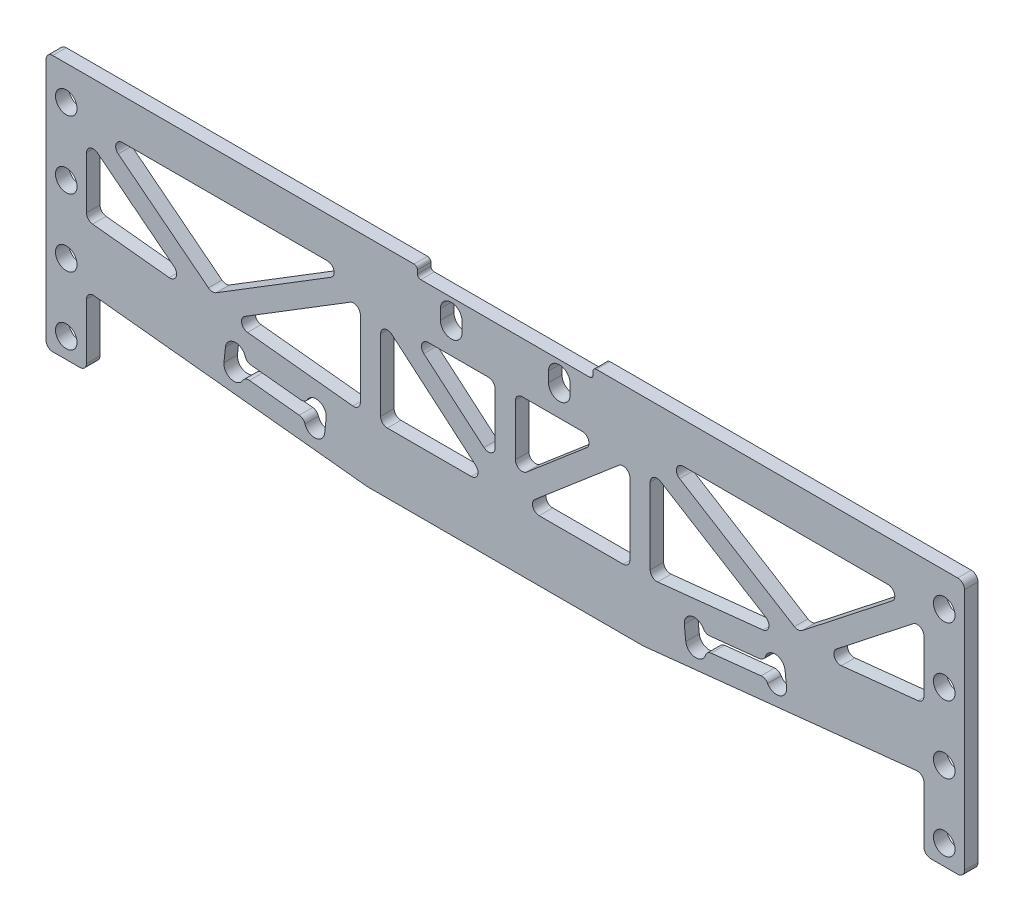
SolidWorks part; units mm, degrees
material "Thornel Mat VMA"
ref_plane "前视基准面" through (0, 0, 0) normal (0, 0, 1) x (1, 0, 0)
ref_plane "上视基准面" through (0, 0, 0) normal (0, 1, 0) x (1, 0, 0)
ref_plane "右视基准面" through (0, 0, 0) normal (1, 0, 0) x (0, 0, -1)
sketch "草图1" plane through (0, 0, 0) normal (0, 0, 1) x (1, 0, 0)
  line L1 (-68, 20) -> (68, 20)
  line L2 (-68, 20) -> (-68, -20)
  line L3 (-68, -20) -> (68, -20)
  line L4 (68, 20) -> (68, -20)
  line L5 (-68, 20) -> (68, -20) construction
  line L6 (-68, -20) -> (68, 20) construction
  point P0 (0, 0)
  dimension "D1" = 136
  dimension "D2" = 40
extrude "凸台-拉伸1" add sketch "草图1" along normal blind 2
sketch "草图3" plane through (0, 0, 2) normal (0, 0, 1) x (1, 0, 0)
  line L0 (-65, 15) -> (-65, -5) construction
  line L1 (-65, -5) -> (65, -5) construction
  line L2 (65, -5) -> (65, 15) construction
  line L3 (-68, 20) -> (-68, -20) construction
  line L4 (68, -20) -> (68, 20) construction
  line L5 (68, 20) -> (-68, 20) construction
  circle A0 centre (65, -5) radius 1.6
  circle A1 centre (65, 15) radius 1.6
  circle A2 centre (-65, 15) radius 1.6
  circle A3 centre (-65, -5) radius 1.6
  dimension "D5" = 3.2
  dimension "D1" = 3
  dimension "D2" = 3
  dimension "D3" = 20
  dimension "D4" = 5
extrude "切除-拉伸3" cut sketch "草图3" against normal through all
sketch "草图6" plane through (0, 0, 2) normal (0, 0, 1) x (1, 0, 0)
  line L0 (41.5406, -5.6675) -> (26.6228, -7.2355) construction
  line L1 (-68, -20) -> (68, -20) construction
  line L2 (0, 0) -> (0, -20) construction
  line L3 (41.4309, -4.6233) -> (26.5131, -6.1912)
  line L4 (41.6504, -6.7118) -> (26.7326, -8.2797)
  line L5 (28.2244, -8.1229) -> (28.0048, -6.0344) construction
  line L6 (26.7326, -8.2797) -> (26.5131, -6.1912)
  line L7 (29.7161, -7.9661) -> (29.4966, -5.8776)
  line L8 (39.9391, -4.7801) -> (40.1586, -6.8686) construction
  line L9 (41.4309, -4.6233) -> (41.6504, -6.7118)
  line L10 (38.4473, -4.9369) -> (38.6668, -7.0254)
  arc A0 (26.7326, -8.2797) -> (29.7161, -7.9661) centre (28.2244, -8.1229) ccw
  arc A1 (29.4966, -5.8776) -> (26.5131, -6.1912) centre (28.0048, -6.0344) ccw
  arc A2 (41.4309, -4.6233) -> (38.4473, -4.9369) centre (39.9391, -4.7801) ccw
  arc A3 (38.6668, -7.0254) -> (41.6504, -6.7118) centre (40.1586, -6.8686) ccw
  point P13 (28.1146, -7.0787)
  point P18 (40.0489, -5.8243)
  dimension "D5" = 1.5
  dimension "D1" = 15
  dimension "D2" = 6
  dimension "D3" = 1.05
  dimension "D4" = 1.05
extrude "切除-拉伸5" cut sketch "草图6" against normal through all contours L3 A1 | L4 L7 L3 L6 | L4 A0 | L10 L3 L7 L4 | L3 L10 L4 L9 | L3 A2 | L4 A3 region at (40.0489, -5.8243, 2) region at (39.8726, -4.147, 2) region at (34.0817, -6.4515, 2) region at (40.2252, -7.5017, 2) region at (28.1146, -7.0787, 2) region at (27.9383, -5.4013, 2) region at (28.2909, -8.7561, 2)
mirror "镜向1" about plane through (0, 0, 0) normal (1, 0, 0) of "切除-拉伸5"
sketch "草图7" plane through (0, 0, 2) normal (0, 0, 1) x (1, 0, 0)
  line L0 (68, -20) -> (68, 20) construction
  line L1 (-68, -20) -> (68, -20)
  line L2 (-68, -20) -> (-68, -12)
  line L3 (-68, -12) -> (68, -12)
  line L4 (68, -20) -> (68, -12)
  dimension "D1" = 8
extrude "切除-拉伸6" cut sketch "草图7" against normal through all
sketch "草图8" plane through (0, 0, 2) normal (0, 0, 1) x (1, 0, 0)
  line L0 (-68, -7) -> (-68, -12)
  line L1 (-68, 20) -> (-68, -12) construction
  line L2 (-68, -12) -> (-20.4282, -12)
  line L3 (68, -12) -> (-68, -12) construction
  line L4 (-20.4282, -12) -> (-68, -7)
  line L5 (0, 0) -> (0, -12) construction
  line L6 (20.4282, -12) -> (68, -7)
  line L7 (68, -12) -> (20.4282, -12)
  line L8 (68, -7) -> (68, -12)
  dimension "D1" = 5
  dimension "D2" = 6
extrude "切除-拉伸7" cut sketch "草图8" against normal through all
sketch "草图9" plane through (0, 0, 2) normal (0, 0, 1) x (1, 0, 0)
  line L0 (-67.0592, 1.9507) -> (-19.9565, -3)
  line L1 (-19.9565, -3) -> (19.9565, -3)
  line L2 (19.9565, -3) -> (67.0592, 1.9507)
  line L3 (62, -7) -> (62, 14)
  line L4 (62, 14) -> (-62, 14)
  line L5 (-62, 14) -> (-62, -7)
  line L6 (-68, -7) -> (-20.4282, -12)
  line L7 (-20.4282, -12) -> (20.4282, -12)
  line L8 (20.4282, -12) -> (68, -7)
  line L9 (68, -7) -> (68, 20)
  line L10 (68, 20) -> (-68, 20)
  line L11 (-68, 20) -> (-68, -7)
  line L12 (-68, -7) -> (-20.4282, -12)
  line L13 (-20.4282, -12) -> (20.4282, -12)
  line L14 (20.4282, -12) -> (68, -7)
  line L15 (68, -7) -> (68, 20)
  line L16 (68, 20) -> (-68, 20)
  line L17 (-68, 20) -> (-68, -7)
  line L18 (-19.9565, -3) -> (-19.9565, 14)
  line L19 (19.9565, -3) -> (19.9565, 14)
  line L20 (-19.9565, 14) -> (0, -3)
  line L21 (0, -3) -> (0, 14)
  line L22 (19.9565, 14) -> (0, -3)
  line L23 (19.9565, 14) -> (43.5079, -0.5247)
  line L24 (43.5079, -0.5247) -> (62, 14)
  line L25 (-19.9565, 14) -> (-43.5079, -0.5247)
  line L26 (-43.5079, -0.5247) -> (-62, 14)
  line L27 (-20.7439, 15.2767) -> (-43.4044, 1.3015)
  line L28 (-43.4044, 1.3015) -> (-61.0735, 15.1796)
  line L29 (-20.9292, 12.8581) -> (-0.9727, -4.1419)
  line L30 (18.9838, 15.1419) -> (-0.9727, -1.8581)
  line L31 (-18.4565, -3) -> (-18.4565, 14)
  line L32 (21.4565, -3) -> (21.4565, 14)
  line L33 (19.1691, 12.7233) -> (43.6113, -2.3508)
  line L34 (43.6113, -2.3508) -> (62.9265, 12.8204)
  line L35 (1.5, -3) -> (1.5, 14)
  line L36 (-19.1691, 12.7233) -> (-43.6113, -2.3508)
  line L37 (-43.6113, -2.3508) -> (-62.9265, 12.8204)
  line L38 (-18.9838, 15.1419) -> (0.9727, -1.8581)
  line L39 (20.9292, 12.8581) -> (0.9727, -4.1419)
  line L40 (-21.4565, -3) -> (-21.4565, 14)
  line L41 (18.4565, -3) -> (18.4565, 14)
  line L42 (20.7439, 15.2767) -> (43.4044, 1.3015)
  line L43 (43.4044, 1.3015) -> (61.0735, 15.1796)
  line L44 (-1.5, -3) -> (-1.5, 14)
  line L45 (14.1216, 11) -> (-14.1216, 11)
  dimension "D6" = 3
  dimension "D1" = 0
  dimension "D2" = 9
  dimension "D3" = 6
  dimension "D4" = 1.5
  dimension "D5" = 1.5
extrude "切除-拉伸8" cut sketch "草图9" against normal through all flip side to cut contours L1 L41 L39 | L33 L32 L2 | L42 L43 L4 | L34 L2 L3 | L30 L45 L35 | L44 L45 L38 | L31 L1 L29 | L0 L40 L36 | L28 L27 L4 | L0 L37 L5 | L12 L13 L14 L15 L16 L17 region at (-56.7705, 4.4272, 2) region at (-27.9931, 2.563, 2) region at (-41.93, 9.7672, 2) region at (-13.0754, 1.5839, 2) region at (-5.7072, 7.4161, 2) region at (13.0754, 1.5839, 2) region at (5.7072, 7.4161, 2) region at (27.9931, 2.563, 2) region at (41.93, 9.7672, 2) region at (56.7705, 4.4272, 2)
fillet "圆角2" radius 1 6 edges at (-68, -7, 1) (68, 20, 1) (68, -7, 1) (20.4282, -12, 1) (-20.4282, -12, 1) (-68, 20, 1)
fillet "圆角3" radius 1 38 edges at (1.5, 0.2482, 1) (1.5, 11, 1) (14.1216, 11, 1) (41.0664, -0.7813, 1) (21.4565, -2.8423, 1) (21.4565, 11.3126, 1) (59.5716, 14, 1) (43.4044, 1.3015, 1) (22.8141, 14, 1) (-59.5716, 14, 1) (-22.8141, 14, 1) (-43.4044, 1.3015, 1) (-21.4565, 11.3126, 1) (-21.4565, -2.8423, 1) (-41.0664, -0.7813, 1) (-62, 12.0926, 1) (-46.3114, -0.23, 1) (-62, 1.4189, 1) (18.4565, 10.7518, 1) (18.4565, -3, 1) (2.3131, -3, 1) (38.4473, -4.9369, 1) (38.6668, -7.0254, 1) (29.7161, -7.9661, 1) (29.4966, -5.8776, 1) (-29.7161, -7.9661, 1) (-38.6668, -7.0254, 1) (-38.4473, -4.9369, 1) (-29.4966, -5.8776, 1) (-14.1216, 11, 1) (-1.5, 11, 1) (-1.5, 0.2482, 1) (-18.4565, 10.7518, 1) (-2.3131, -3, 1) (-18.4565, -3, 1) (62, 12.0926, 1) (46.3114, -0.23, 1) (62, 1.4189, 1)
sketch "草图11" plane through (0, 0, 0) normal (0, 0, -1) x (-1, 0, 0)
  line L0 (-67, 20) -> (67, 20) construction
  line L1 (-8, 24.5) -> (8, 24.5) construction
  line L2 (-8, 24.5) -> (-8, 15.5) construction
  line L3 (-8, 15.5) -> (8, 15.5) construction
  line L4 (8, 24.5) -> (8, 15.5) construction
  line L5 (-8, 24.5) -> (8, 15.5) construction
  line L6 (-8, 15.5) -> (8, 24.5) construction
  line L7 (-8, 16.25) -> (-8, 14.75) construction
  line L8 (-6.4, 16.25) -> (-6.4, 14.75)
  line L9 (-9.6, 16.25) -> (-9.6, 14.75)
  line L10 (8, 16.25) -> (8, 14.75) construction
  line L11 (9.6, 16.25) -> (9.6, 14.75)
  line L12 (6.4, 16.25) -> (6.4, 14.75)
  line L14 (-13, 21.5) -> (13, 21.5)
  line L15 (-13, 21.5) -> (-13, 18.5)
  line L16 (-13, 18.5) -> (13, 18.5)
  line L17 (13, 21.5) -> (13, 18.5)
  line L18 (-13, 21.5) -> (13, 18.5) construction
  line L19 (-13, 18.5) -> (13, 21.5) construction
  arc A0 (-6.4, 16.25) -> (-9.6, 16.25) centre (-8, 16.25) ccw
  arc A1 (-9.6, 14.75) -> (-6.4, 14.75) centre (-8, 14.75) ccw
  arc A2 (9.6, 16.25) -> (6.4, 16.25) centre (8, 16.25) ccw
  arc A3 (6.4, 14.75) -> (9.6, 14.75) centre (8, 14.75) ccw
  point P0 (0, 20)
  point P10 (-8, 15.5)
  point P17 (8, 15.5)
  point P23 (0, 20)
  dimension "D4" = 1.6
  dimension "D1" = 9
  dimension "D2" = 16
  dimension "D3" = 1.5
  dimension "D5" = 3
  dimension "D6" = 26
extrude "切除-拉伸9" cut sketch "草图11" against normal through all
fillet "圆角4" radius 0.5 4 edges at (13, 20, 1) (13, 18.5, 1) (-13, 20, 1) (-13, 18.5, 1)
sketch "草图13" plane through (0, 0, 0) normal (0, 0, -1) x (-1, 0, 0)
  line L0 (-65, 15) -> (-65, 5) construction
  line L1 (-65, 5) -> (-65, -15) construction
  line L2 (-68, -6.0996) -> (-68, 19) construction
  line L3 (-62, -18) -> (-68, -18)
  line L4 (-62, -18) -> (-62, 10)
  line L5 (-62, 10) -> (-68, 10)
  line L6 (-68, -18) -> (-68, 10)
  line L7 (-62, -18) -> (-68, 10) construction
  line L8 (-62, 10) -> (-68, -18) construction
  line L9 (0, 0) -> (0, -50000) construction
  line L10 (62, 10) -> (68, 10)
  line L11 (68, -18) -> (68, 10)
  line L12 (62, -18) -> (68, -18)
  line L13 (62, -18) -> (62, 10)
  circle A0 centre (-65, 5) radius 1.6 construction
  circle A1 centre (-65, -15) radius 1.6
  circle A2 centre (-65, -5) radius 1.6 construction
  circle A3 centre (-65, 15) radius 1.6 construction
  circle A4 centre (65, -15) radius 1.6
  point P8 (-65, -4)
  dimension "D1" = 10
  dimension "D3" = 3
  dimension "D2" = 20
  dimension "D4" = 5
extrude "凸台-拉伸2" add sketch "草图13" against normal up to surface (2 mm away) up to face at (0, 7.8846, 2)
sketch "草图14" plane through (0, 0, 0) normal (0, 0, -1) x (-1, 0, 0)
  line L0 (-65, 15) -> (-65, 5) construction
  line L1 (-65, 5) -> (-65, -5) construction
  circle A0 centre (-65, 5) radius 1.6
  circle A1 centre (-65, -5) radius 1.6
  circle A2 centre (-65, -15) radius 1.6 construction
  dimension "D1" = 10
  dimension "D2" = 10
extrude "切除-拉伸10" cut sketch "草图14" against normal blind 10
fillet "圆角5" radius 1 3 edges at (68, -18, 1) (62, -18, 1) (62, -7.6306, 1)
mirror "镜向4" about plane through (0, 0, 0) normal (1, 0, 0) of "切除-拉伸10"
fillet "圆角6" radius 1 3 edges at (-68, -18, 1) (-62, -18, 1) (-62, -7.6306, 1)
